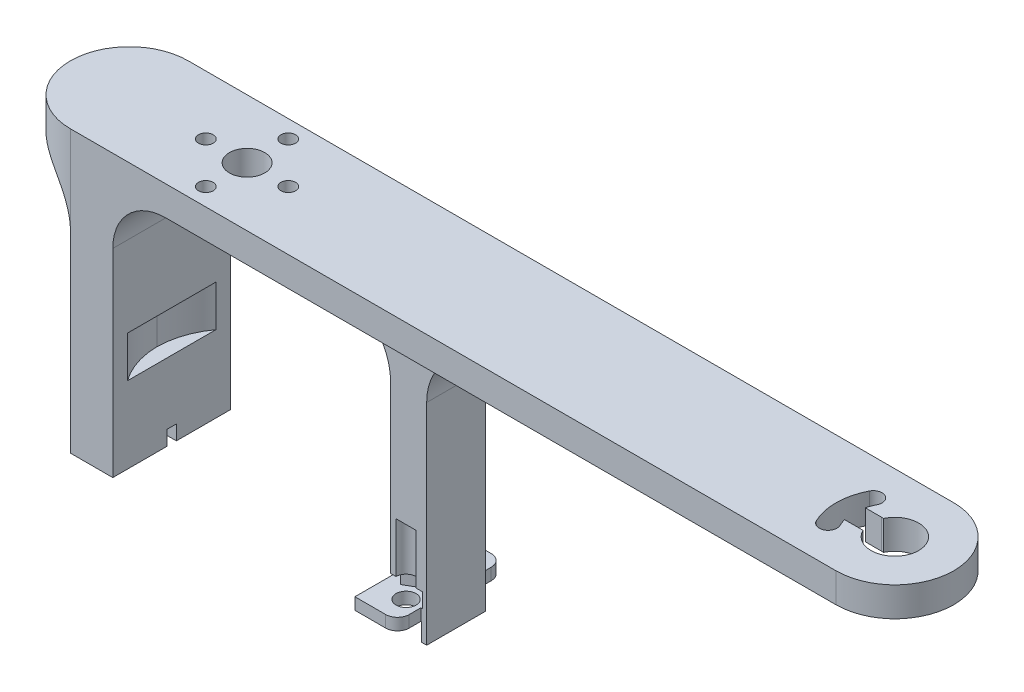
SolidWorks part; units mm, degrees
note: The reader was unsure of these and kept them because the rebuilt part matched: shared geometry of "Esquisse12<3>".
ref_plane "Front Plane" through (0, 0, 0) normal (0, 0, 1) x (1, 0, 0)
ref_plane "Top Plane" through (0, 0, 0) normal (0, 1, 0) x (1, 0, 0)
ref_plane "Right Plane" through (0, 0, 0) normal (1, 0, 0) x (0, 0, -1)
sketch "Sketch1" plane through (0, 0, 0) normal (0, 1, 0) x (1, 0, 0)
  line L0 (0, 0) -> (110, 0) construction
  line L1 (0, 10) -> (110, 10)
  line L2 (0, -10) -> (110, -10)
  line L3 (0, 10) -> (-10, 10)
  line L4 (-20, 0) -> (-20, -10) construction
  line L5 (-10, -10) -> (0, -10)
  line L6 (-20, 10) -> (-20, 0) construction
  line L7 (-20, -10) -> (-10, -10) construction
  line L8 (-10, 10) -> (-20, 10) construction
  line L9 (-20, 10) -> (-10, 10)
  line L10 (-10, -10) -> (-20, -10)
  arc A0 (0, 10) -> (0, -10) centre (0, 0) ccw construction
  arc A1 (110, -10) -> (110, 10) centre (110, 0) ccw
  arc A2 (-10, 10) -> (-10, -10) centre (-10, 0) ccw construction
  arc A3 (-20, 10) -> (-20, -10) centre (-20, 0) ccw
  point P3 (55, 0)
  dimension "D1" = 2
extrude "Boss-Extrude1" add sketch "Sketch1" along normal blind 5 contours L3 A2 L5 L2 A1 L1
sketch "Sketch7" [suppressed] plane through (0, 0, 0) normal (0, -1, 0) x (1, 0, 0)
  line L0 (-20.1298, 0) -> (-17.1298, 0) construction
  line L1 (0, 10) -> (-20.1298, 10)
  line L2 (0, 10) -> (0, -10) construction
  line L3 (0, -10) -> (-20.1298, -10)
  line L4 (-20.1298, 10) -> (-20.1298, -10)
  line L5 (-17.1298, -4.1696) -> (-17.1298, 4.1696) construction
  arc A1 (0, 10) -> (0, -10) centre (0, 0) ccw
extrude "Boss-Extrude5" [suppressed] add sketch "Sketch7" against normal up to surface (5 mm away)
sketch "Sketch2" plane through (0, 5, 0) normal (0, 1, 0) x (1, 0, 0)
  circle A4 centre (0, 0) radius 3
  circle A10 centre (7, 0) radius 1.25
  circle A11 centre (-7, 0) radius 1.25
  circle A12 centre (0, -7) radius 1.25
  circle A13 centre (0, 7) radius 1.25
  point P24 (0, 0)
extrude "Cut-Extrude1" cut sketch "Sketch2" against normal up to surface (5 mm away) up to face at (45, 0, 0)
sketch "Esquisse5" plane through (0, 0, 0) normal (0, -1, 0) x (1, 0, 0)
  circle A0 centre (-7, 0) radius 1.25 construction
  circle A1 centre (-7, 0) radius 1.25
  circle A3 centre (0, 7) radius 1.7
  circle A6 centre (0, 7) radius 1.25 construction
  circle A7 centre (7, 0) radius 1.25 construction
  circle A8 centre (0, -7) radius 1.25 construction
  circle A9 centre (0, 7) radius 1.25
  circle A10 centre (7, 0) radius 1.25
  circle A11 centre (0, -7) radius 1.25
  circle A12 centre (7, 0) radius 1.7
  circle A13 centre (0, -7) radius 1.7
  circle A14 centre (-7, 0) radius 1.7
  point P22 (0, 0)
  dimension "D1" = 4
extrude "Enlèv. mat.-Extru.3" cut sketch "Esquisse5" against normal blind 1.5
sketch "Esquisse2" plane through (0, 0, 0) normal (0, -1, 0) x (1, 0, 0)
  line L0 (105.95, 0) -> (101.75, 0) construction
  line L1 (105.95, -1.75) -> (103.2223, -1.75)
  line L2 (105.95, 1.75) -> (103.2223, 1.75)
  line L3 (101.75, 1.75) -> (101.75, -1.75) construction
  line L4 (105.95, 1.75) -> (106.3476, 1.75)
  line L5 (105.95, -1.75) -> (106.3476, -1.75) construction
  line L6 (103.2223, 1.75) -> (101.75, 1.75) construction
  line L7 (103.2223, -1.75) -> (101.75, -1.75) construction
  arc A0 (106.3281, -1.7087) -> (106.3281, 1.7087) centre (110, 0) ccw
  arc A1 (102.329, 3.6614) -> (102.44, -3.8854) centre (110, 0) ccw construction
  arc A2 (110, -10) -> (110, 10) centre (110, 0) ccw construction
  arc A3 (105.95, -1.75) -> (106.3281, -1.7087) centre (105.95, 0) ccw
  arc A4 (101.75, 1.75) -> (101.6818, 1.7487) centre (101.75, 0) ccw
  arc A5 (100.9753, 4.3075) -> (101.1059, -4.5711) centre (110, 0) ccw
  arc A6 (103.6827, 3.0153) -> (103.2223, 1.75) centre (110, 0) ccw
  arc A7 (103.6827, 3.0153) -> (100.9753, 4.3075) centre (102.329, 3.6614) ccw
  arc A8 (101.1059, -4.5711) -> (103.7741, -3.1997) centre (102.44, -3.8854) ccw
  arc A9 (106.3281, 1.7087) -> (105.95, 1.75) centre (105.95, 0) ccw construction
  arc A10 (106.3281, -1.7087) -> (106.3281, 1.7087) centre (105.95, 0) ccw construction
  arc A11 (106.3281, 1.7087) -> (105.95, 0) centre (110, 0) ccw construction
  arc A12 (105.95, 0) -> (106.3281, -1.7087) centre (110, 0) ccw construction
  arc A13 (103.2223, -1.75) -> (103.7741, -3.1997) centre (110, 0) ccw
  arc A14 (103.2223, 1.75) -> (103, 0) centre (110, 0) ccw construction
  arc A15 (103, 0) -> (103.2223, -1.75) centre (110, 0) ccw construction
  arc A16 (101.6818, -1.7487) -> (101.75, -1.75) centre (101.75, 0) ccw
  arc A17 (100, 0) -> (101.6818, -1.7487) centre (101.75, 0) ccw construction
  arc A18 (101.6818, 1.7487) -> (100, 0) centre (101.75, 0) ccw construction
  point P8 (103.85, 0)
  point P16 (120, 0)
  point P20 (101.5009, -0.125)
  dimension "D1" = 10
extrude "Enlèv. mat.-Extru.2" cut sketch "Esquisse2" against normal up to surface (5 mm away)
sketch "Esquisse6" plane through (0, 0, 0) normal (0, -1, 0) x (1, 0, 0)
  line L0 (-10, 10) -> (-6, 10) construction
  line L1 (-6, -10) -> (-10, -10) construction
  line L2 (-10, 10) -> (-10, 9.1652) construction
  line L3 (-10, -10) -> (-10, -9.1652) construction
  line L4 (-12.8, -9.6) -> (-12.8, -10)
  line L5 (29.3702, 5) -> (34.3702, 5)
  line L6 (29.3702, 5) -> (29.3702, -5)
  line L7 (29.3702, -5) -> (34.3702, -5)
  line L8 (34.3702, 5) -> (34.3702, -5) construction
  line L9 (-12.8, -9.6) -> (-12.8, -7.3321)
  line L10 (-10, 0) -> (-20, 0) construction
  line L11 (-12.8, 9.6) -> (-12.8, 7.3321)
  line L12 (-12.8, -10) -> (-20, -10)
  line L13 (34.3702, 5) -> (35.5002, 5)
  line L14 (34.3702, 5) -> (34.3702, -5) construction
  line L15 (34.3702, -5) -> (35.5002, -5)
  line L16 (35.5002, 5) -> (35.5002, -5)
  line L17 (-20, -10) -> (-20, 10)
  line L18 (-20, 10) -> (-12.8, 10)
  line L19 (110, 10) -> (-20, 10) construction
  line L20 (-12.8, 10) -> (-12.8, 9.6)
  line L21 (-12.8, 7.3321) -> (-12.8, -7.3321)
  arc A1 (-12.8, 9.6) -> (-12.8, -9.6) centre (-10, 0) ccw construction
  arc A2 (-12.8, 7.3321) -> (-12.8, -7.3321) centre (-6, 0) ccw construction
  arc A3 (-10, -9.1652) -> (-6, -10) centre (-6, 0) ccw construction
  arc A4 (-6, 10) -> (-10, 9.1652) centre (-6, 0) ccw construction
  arc A6 (-10, 10) -> (-12.8, 9.6) centre (-10, 0) ccw construction
  arc A7 (-10, 9.1652) -> (-12.8, 7.3321) centre (-6, 0) ccw construction
  arc A8 (-12.8, -7.3321) -> (-10, -9.1652) centre (-6, 0) ccw construction
  arc A9 (-12.8, -9.6) -> (-10, -10) centre (-10, 0) ccw construction
  point P14 (29.3702, 0)
  dimension "D1" = 5
  dimension "D2" = 10
  dimension "D3" = 2.8
extrude "Boss.-Extru.1" add sketch "Esquisse6" along normal blind 42.7
sketch "Esquisse9" plane through (0, -42.7, 0) normal (0, -1, 0) x (1, 0, 0)
  line L0 (35.5002, 5) -> (29.3702, 5) construction
  line L1 (29.3702, -5) -> (35.5002, -5) construction
  line L2 (32.5, 8.9616) -> (27.2731, 8.9616)
  line L3 (34.5, 4.5926) -> (34.5, -3.7466)
  line L4 (27.2731, -8.9616) -> (32.5, -8.9616)
  line L5 (-12.8, 8.9616) -> (-18, 8.9616)
  line L6 (-12.8, -8.9616) -> (-18, -8.9616)
  line L7 (-20, -5.2226) -> (-20, -6.9616)
  line L8 (-20, -6.9616) -> (34.5, -6.9616) construction
  line L9 (7.25, -6.9616) -> (7.25, 10) construction
  line L10 (-12.8, 10) -> (110, 10) construction
  line L11 (-20, 0) -> (7.25, 0) construction
  line L12 (-20, 5.2226) -> (-20, 6.9616)
  line L13 (-20, 4.5926) -> (-20, -3.7466)
  line L14 (-20, 5.2226) -> (-20, 4.5926)
  line L15 (-20, -5.2226) -> (-20, -3.7466)
  line L16 (-12.6731, 8.9616) -> (-12.6731, 0.8) construction
  line L17 (27.1731, 0.8) -> (27.1731, -0.8) construction
  line L18 (34.5, -5.2226) -> (34.5, -6.9616)
  line L19 (34.5, -5.2226) -> (34.5, -3.7466)
  line L20 (34.5, 5.2226) -> (34.5, 4.5926)
  line L21 (34.5, 5.2226) -> (34.5, 6.9616)
  line L22 (32.8731, 0.8) -> (32.8731, -0.8) construction
  line L23 (-12.6731, 0.8) -> (-18.3731, 0.8) construction
  line L24 (-12.6731, 0.8) -> (-12.6731, -0.8)
  line L25 (-12.6731, -0.8) -> (-18.3731, -0.8) construction
  line L26 (-18.3731, 0.8) -> (-18.3731, -0.8) construction
  line L27 (27.1731, -0.8) -> (32.8731, -0.8) construction
  line L28 (27.1731, 0.8) -> (32.8731, 0.8) construction
  line L29 (27.2731, 8.9616) -> (27.2731, -8.9616)
  line L30 (27.2731, 8.9616) -> (27.1731, 8.9616) construction
  line L31 (27.1731, 8.9616) -> (27.1731, 0.8) construction
  line L32 (27.1731, -6.9616) -> (27.1731, -8.9616) construction
  line L33 (27.1731, -0.8) -> (27.1731, -6.9616) construction
  line L34 (27.1731, -8.9616) -> (27.2731, -8.9616) construction
  line L35 (-12.8, 8.9616) -> (-12.8, -8.9616)
  line L36 (-12.8, -10) -> (-12.8, 10) construction
  line L37 (-12.8, -10) -> (-12.8, 10) construction
  line L38 (-12.6731, -8.9616) -> (-12.8, -8.9616) construction
  line L39 (-12.6731, -6.9616) -> (-12.6731, -8.9616) construction
  line L40 (-12.6731, -0.8) -> (-12.6731, -6.9616) construction
  line L41 (-12.6731, 0) -> (-12.6731, -0.8) construction
  line L42 (-12.6731, 0.8) -> (-12.6731, 0) construction
  line L43 (-12.6731, 8.9616) -> (-12.8, 8.9616) construction
  circle A0 centre (32, 5) radius 2 construction
  circle A1 centre (32, -5) radius 2 construction
  arc A2 (32.5, -8.9616) -> (34.5, -6.9616) centre (32.5, -6.9616) ccw
  circle A3 centre (-17.5, 5) radius 2 construction
  circle A4 centre (-17.5, -5) radius 2 construction
  arc A5 (-20, -6.9616) -> (-18, -8.9616) centre (-18, -6.9616) ccw
  arc A7 (-20, 6.9616) -> (-18, 8.9616) centre (-18, 6.9616) cw
  arc A8 (34.5, 6.9616) -> (32.5, 8.9616) centre (32.5, 6.9616) ccw
  point P50 (-18.3731, 0)
  line M1 (29.3702, 5) -> (29.3702, -5)
  line M2 (29.3702, -5) -> (35.5002, -5)
  line M4 (35.5002, 5) -> (29.3702, 5)
  dimension "D1" = 0.1
  dimension "D2" = 0.1269
extrude "Boss.-Extru.4" add sketch "Esquisse9" against normal blind 2 contours A7 L12 L14 L13 L15 L7 A5 L6 L16 L5 | L21 A8 L2 L17 L4 A2 L18 L19 L20 M2 M1 M4 | L20 L19 L3 M4 M1 M2
sketch "Esquisse12" plane through (0, -42.7, 0) normal (0, -1, 0) x (1, 0, 0)
  line L0 (34.5, -5.2226) -> (34.5, -6.9616) construction
  line L1 (34.5, -5.2226) -> (34.5, -3.7466) construction
  line L2 (34.5, 4.5926) -> (34.5, -3.7466) construction
  line L3 (34.5, 5.2226) -> (34.5, 4.5926) construction
  line L4 (34.5, 5.2226) -> (34.5, 6.9616) construction
  line L5 (34.5, -5.2226) -> (34.5, -6.9616) construction
  line L6 (34.5, -5.2226) -> (34.5, -3.7466) construction
  line L7 (34.5, 4.5926) -> (34.5, -3.7466) construction
  line L8 (34.5, 5.2226) -> (34.5, 4.5926) construction
  line L9 (34.5, 5.2226) -> (34.5, 6.9616) construction
  line L10 (35.5002, -5.2226) -> (35.5002, -6.9616) construction
  line L11 (35.5002, 4.5926) -> (35.5002, -3.7466) construction
  line L12 (35.5002, -5.2226) -> (35.5002, -3.7466) construction
  line L13 (35.5002, 5.2226) -> (35.5002, 4.5926) construction
  line L14 (35.5002, 5.2226) -> (35.5002, 6.9616) construction
  line L15 (33.5002, 8.9616) -> (32.5, 8.9616) construction
  line L16 (33.5002, -8.9616) -> (32.5, -8.9616) construction
  line L17 (35.5002, 5) -> (34.5, 5) construction
  line L18 (35.5002, -6.9616) -> (34.5, -6.9616) construction
  line L19 (34.65, 5) -> (34.65, -5) construction
  line L20 (29.3702, -5) -> (35.5002, -5) construction
  line L22 (34.65, 5) -> (35.5002, 5)
  line L23 (34.65, 5) -> (34.65, -5)
  line L24 (34.65, -5) -> (35.5002, -5)
  line L25 (35.5002, 5) -> (35.5002, -5)
  circle A4 centre (-17.5, -5) radius 1.7
  circle A5 centre (-17.5, 5) radius 1.7
  circle A6 centre (32, -5) radius 1.7
  circle A7 centre (32, 5) radius 1.7
  arc A8 (32.5, -8.9616) -> (34.5, -6.9616) centre (32.5, -6.9616) ccw construction
  arc A9 (34.5, 6.9616) -> (32.5, 8.9616) centre (32.5, 6.9616) ccw construction
  arc A10 (32.5, -8.9616) -> (34.5, -6.9616) centre (32.5, -6.9616) ccw construction
  arc A11 (34.5, 6.9616) -> (32.5, 8.9616) centre (32.5, 6.9616) ccw construction
  arc A12 (33.5002, -8.9616) -> (35.5002, -6.9616) centre (33.5002, -6.9616) ccw construction
  arc A13 (35.5002, 6.9616) -> (33.5002, 8.9616) centre (33.5002, 6.9616) ccw construction
  line M3 (34.5, -5) -> (35.5002, -5)
  line M4 (35.5002, -5) -> (35.5002, 5)
  line M5 (35.5002, 5) -> (34.5, 5)
  dimension "D1" = 0.15
  dimension "D2" = 3.4
extrude "Boss.-Extru.9" add sketch "Esquisse12" along normal blind 3 contours L23 M5 M3 M4 | A6 | A7
sketch "Esquisse13" plane through (0, -42.7, 0) normal (0, -1, 0) x (1, 0, 0)
  line L1 (27.2731, 8.9616) -> (27.2731, -8.9616) construction
  line L6 (32.9731, 0.8) -> (32.9731, -0.8)
  line L7 (27.2731, -0.8) -> (32.9731, -0.8)
  line L8 (27.2731, 0.8) -> (32.9731, 0.8)
  line L9 (-12.8, -0.8) -> (-18.5, -0.8)
  line L10 (-18.5, 0.8) -> (-18.5, -0.8)
  line L11 (-12.8, 0.8) -> (-18.5, 0.8)
  line L12 (27.2731, 0.8) -> (27.2731, -0.8)
  line L13 (-12.8, 0.8) -> (-12.8, -0.8)
  line L14 (-12.8, -10) -> (-12.8, 10) construction
extrude "Enlèv. mat.-Extru.4" cut sketch "Esquisse13" against normal blind 2.5
extrude "Cut-Extrude2" cut sketch "Esquisse12<3>" against normal blind 13 contours A7 | A6 | A4 | A5
sketch "Esquisse12<3>" plane through (0, -42.7, 0) normal (0, -1, 0) x (1, 0, 0) same geometry as "Esquisse12"
fillet "Fillet1" radius 10 3 edges at (-20, 0, 0) (35.5002, 0, 0) (29.3702, 0, 0) tangent propagation no
fillet "Fillet2" radius 9 1 edges at (-12.8, 0, 0) tangent propagation no
sketch "Sketch10" plane through (0, -40.7, 0) normal (0, 1, 0) x (1, 0, 0)
  line L0 (-20, 10) -> (110, 10) construction
  line L1 (32, 8.2332) -> (29.2, 6.6166)
  line L2 (29.2, 6.6166) -> (29.2, 3.3834)
  line L3 (29.2, 3.3834) -> (32, 1.7668)
  line L4 (32, 1.7668) -> (34.8, 3.3834)
  line L5 (34.8, 3.3834) -> (34.8, 6.6166)
  line L6 (34.8, 6.6166) -> (32, 8.2332)
  line L7 (29.2, -6.6166) -> (32, -8.2332)
  line L8 (32, -1.7668) -> (29.2, -3.3834)
  line L9 (29.2, -3.3834) -> (29.2, -6.6166)
  line L12 (34.8, -3.3834) -> (32, -1.7668)
  line L18 (34.8, -6.6166) -> (34.8, -3.3834)
  line L19 (32, -8.2332) -> (34.8, -6.6166)
  line L20 (-20.3, -3.3834) -> (-20.3, -6.6166)
  line L21 (-14.7, -6.6166) -> (-14.7, -3.3834)
  line L22 (-17.5, -1.7668) -> (-20.3, -3.3834)
  line L23 (-17.5, -8.2332) -> (-14.7, -6.6166)
  line L24 (-14.7, -3.3834) -> (-17.5, -1.7668)
  line L25 (-20.3, -6.6166) -> (-17.5, -8.2332)
  line L26 (-14.7, 6.6166) -> (-17.5, 8.2332)
  line L27 (-20.3, 3.3834) -> (-17.5, 1.7668)
  line L28 (-20.3, 6.6166) -> (-20.3, 3.3834)
  line L29 (-17.5, 1.7668) -> (-14.7, 3.3834)
  line L30 (-14.7, 3.3834) -> (-14.7, 6.6166)
  line L31 (-17.5, 8.2332) -> (-20.3, 6.6166)
  circle A0 centre (32, 5) radius 2.8 construction
  circle A1 centre (32, -5) radius 2.8 construction
  circle A2 centre (32, -5) radius 1.7
  circle A3 centre (32, -5) radius 1.7
  circle A4 centre (32, 5) radius 1.7
  circle A5 centre (32, 5) radius 1.7
  circle A6 centre (-17.5, -5) radius 1.7
  circle A7 centre (-17.5, -5) radius 1.7
  circle A8 centre (-17.5, 5) radius 1.7
  circle A9 centre (-17.5, 5) radius 1.7
  circle A10 centre (-17.5, -5) radius 2.8 construction
  circle A11 centre (-17.5, 5) radius 2.8 construction
  dimension "D5" = 5.6
  dimension "D6" = 5.6
  dimension "D7" = 5.6
  dimension "D8" = 5.6
  dimension "D1" = 0
  dimension "D2" = 0
  dimension "D3" = 0
  dimension "D4" = 0
extrude "Cut-Extrude4" cut sketch "Sketch10" along normal blind 2.5
sketch "Sketch9" plane through (-20, 0, 0) normal (-1, 0, 0) x (0, 0, 1)
  line L0 (8.9616, -40.7) -> (0.8, -40.7) construction
  line L1 (-8.2338, -38.2) -> (-1.7338, -38.2)
  line L2 (-8.2338, -38.2) -> (-8.2338, -40.7)
  line L3 (-8.2338, -40.7) -> (-1.7338, -40.7)
  line L4 (-1.7338, -38.2) -> (-1.7338, -40.7)
  line L5 (1.7368, -38.2) -> (8.2368, -38.2)
  line L6 (1.7368, -38.2) -> (1.7368, -40.7)
  line L7 (1.7368, -40.7) -> (8.2368, -40.7)
  line L8 (8.2368, -38.2) -> (8.2368, -40.7)
  line L9 (-6.7898, -38.2) -> (-3.2102, -38.2) construction
  dimension "D1" = 6.5
extrude "Cut-Extrude3" cut sketch "Sketch9" against normal blind 3
sketch "Sketch11" plane through (-12.8, 0, 0) normal (1, 0, 0) x (0, 0, -1)
  line L0 (6.9616, -42.7) -> (5, -42.7) construction
  line L1 (-7.5, -22.7) -> (7.5, -22.7)
  line L2 (-7.5, -22.7) -> (-7.5, -29.7)
  line L3 (-7.5, -29.7) -> (7.5, -29.7)
  line L4 (7.5, -22.7) -> (7.5, -29.7)
  line L5 (5, -45.7) -> (-5, -45.7) construction
  point P8 (0, -45.7)
  point P9 (0, -29.7)
  dimension "D1" = 13
  dimension "D2" = 20
extrude "Cut-Extrude5" cut sketch "Sketch11" against normal blind 2.5
fillet "Fillet3" radius 13 2 edges at (-15.3, -26.2, -7.5) (-15.3, -26.2, 7.5) tangent propagation no
